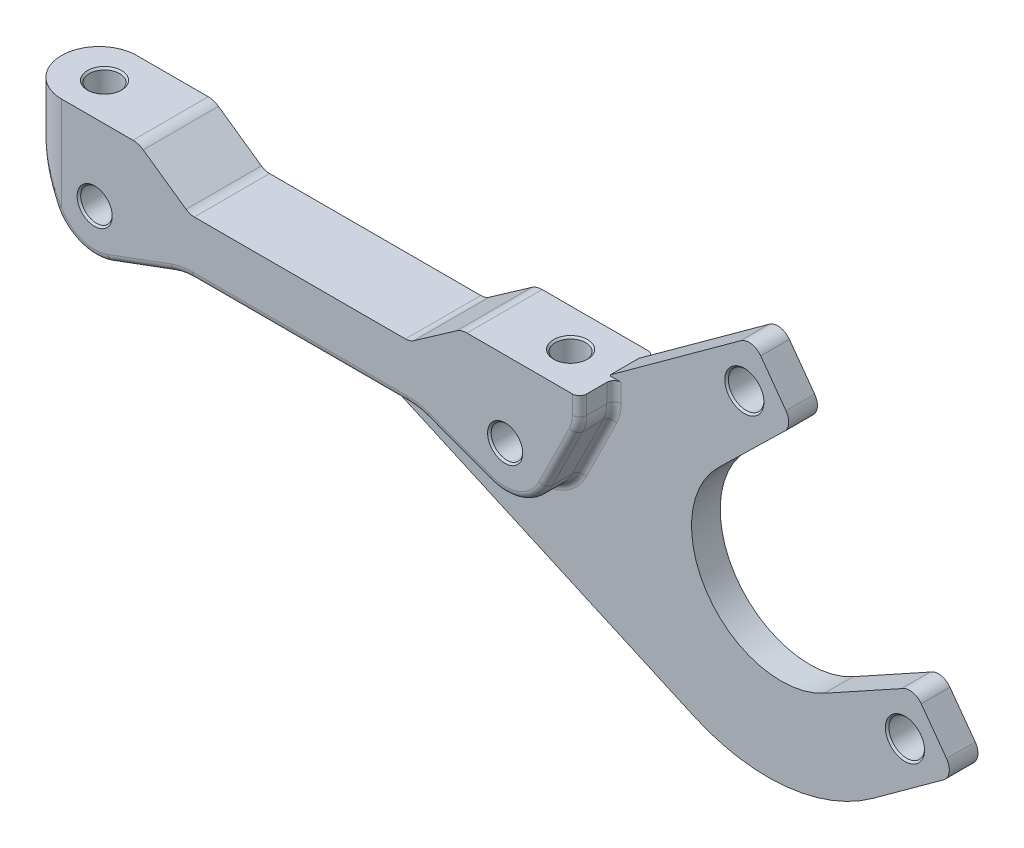
SolidWorks part; units mm, degrees
material "6061-T6 (SS)"
ref_plane "Front Plane" through (0, 0, 0) normal (0, 0, 1) x (1, 0, 0)
ref_plane "Top Plane" through (0, 0, 0) normal (0, 1, 0) x (1, 0, 0)
ref_plane "Right Plane" through (0, 0, 0) normal (1, 0, 0) x (0, 0, -1)
sketch "Sketch1" plane through (0, 0, 0) normal (0, 0, 1) x (1, 0, 0)
  line L0 (-62, 15.9233) -> (-62, -14.304) construction
  line L1 (62, 13.7642) -> (62, -21.0511) construction
  line L2 (-68.4547, -5.5412) -> (-78, 13.76)
  line L3 (-78, 13.76) -> (78, 13.76)
  line L4 (78, 13.76) -> (68.4547, -5.5412)
  line L5 (-73.8283, -12.5) -> (71.5637, -12.5) construction
  line L6 (-26.3177, -4.24) -> (18.9734, -4.24) construction
  line L7 (-30, -4.24) -> (30, -4.24)
  line L8 (-52.9127, -11.7234) -> (-35.2048, -5.1719)
  line L9 (35.2048, -5.1719) -> (52.9127, -11.7234)
  circle A0 centre (-57.25, 0) radius 4.75 construction
  circle A1 centre (57.25, 0) radius 4.75 construction
  arc A2 (-68.4547, -5.5412) -> (-52.9127, -11.7234) centre (-57.25, 0) ccw
  arc A3 (52.9127, -11.7234) -> (68.4547, -5.5412) centre (57.25, 0) ccw
  arc A4 (35.2048, -5.1719) -> (30, -4.24) centre (30, -19.24) ccw
  arc A5 (-30, -4.24) -> (-35.2048, -5.1719) centre (-30, -19.24) ccw
  dimension "D1" = 9.5
  dimension "D2" = 9.5
  dimension "D5" = 25
  dimension "D11" = 15
  dimension "D3" = 124
  dimension "D9" = 156
  dimension "D12" = 60
  dimension "D13" = 30
  dimension "D4" = 62
  dimension "D6" = 18
  dimension "D7" = 26.26
extrude "Boss-Extrude2" add sketch "Sketch1" along normal blind 21
ref_plane "Hub Mounting Plane" through (0, 0, 57) normal (0, 0, 1) x (1, 0, 0)
sketch "Sketch2" plane through (0, 13.76, 0) normal (0, 1, 0) x (1, 0, 0)
  line L0 (78, -21) -> (78, 0) construction
  line L1 (-78, -21) -> (78, -21)
  line L2 (-78, -21) -> (-78, 0)
  line L3 (-78, 0) -> (78, 0)
  line L4 (78, -21) -> (78, 0)
  line L5 (-78, -21) -> (-78, 0) construction
  line L6 (78, -21) -> (-78, -21) construction
  line L7 (78.3439, -10.5) -> (-79.2862, -10.5) construction
  line L8 (78, 0) -> (-78, 0) construction
  circle A0 centre (-65, -10.5) radius 5.05 construction
  circle A1 centre (65, -10.5) radius 5.05 construction
  point P6 (0, 0)
  dimension "D2" = 10.1
  dimension "D3" = 10.1
  dimension "D4" = 130
  dimension "D5" = 65
  dimension "D1" = 10.5
  dimension "D6" = 21
extrude "Boss-Extrude3" add sketch "Sketch2" along normal blind 7.5
fillet "Fillet1" [suppressed] radius 10
sketch "Sketch3" [suppressed] plane through (0, 0, 0) normal (0, 0, -1) x (-1, 0, 0)
  line L0 (-71.9881, 4.5) -> (69.3283, 4.5)
  line L1 (-67.7059, -12.5) -> (67.0774, -12.5) construction
  circle A0 centre (-57.25, 0) radius 4.75
  circle A1 centre (57.25, 0) radius 4.75
  circle A2 centre (-57.25, 0) radius 12.5
  circle A3 centre (57.25, 0) radius 12.5
  arc A4 (-68.4547, -5.5412) -> (-52.9127, -11.7234) centre (-57.25, 0) ccw construction
  dimension "D1" = 17
ref_plane "Plane1" through (0, 0, 0) normal (0, 0, -1) x (-1, 0, 0)
sketch "Sketch5" plane through (0, 21.26, 0) normal (0, 1, 0) x (1, 0, 0)
  circle A0 centre (65, -10.5) radius 5.05 construction
  circle A1 centre (-65, -10.5) radius 5.05 construction
  circle A2 centre (65, -10.5) radius 5.05 construction
  circle A3 centre (-65, -10.5) radius 5.05 construction
sketch "Sketch6" plane through (0, 0, 0) normal (0, 0, -1) x (-1, 0, 0)
  line L2 (29.4573, 11.26) -> (-29.4573, 11.26)
  line L4 (-78, 21.26) -> (78, 21.26) construction
  line L5 (31.7516, 11.9834) -> (45, 21.26)
  line L6 (-45, 21.26) -> (-31.7516, 11.9834)
  line L7 (-45, 21.26) -> (45, 21.26)
  arc A0 (31.7516, 11.9834) -> (29.4573, 11.26) centre (29.4573, 15.26) cw
  arc A1 (-29.4573, 11.26) -> (-31.7516, 11.9834) centre (-29.4573, 15.26) cw
  dimension "D4" = 4
  dimension "D2" = 145
  dimension "D3" = 145
  dimension "D1" = 90
  dimension "D5" = 45
  dimension "D6" = 10
extrude "Cut-Extrude3" cut sketch "Sketch6" against normal up to surface (21 mm away) up to face at (0, 0.932, 21)
fillet "Fillet3" radius 5 2 edges at (-45, 21.26, 10.5) (45, 21.26, 10.5)
fillet "Fillet4" radius 10 2 edges at (-78, 13.76, 10.5) (78, 13.76, 10.5)
sketch "Sketch8" plane through (0, 21.26, 0) normal (0, 1, 0) x (1, 0, 0)
  line L1 (-78, 0) -> (-78, -21)
  line L6 (-65, -10.5) -> (-66.5, -10.5) construction
  line L9 (-77, -0.6837) -> (-77, -19.879) construction
  line L10 (-66.5, 0) -> (-78, 0)
  line L11 (-78, -21) -> (-66.5, -21)
  line L12 (0, 15.9579) -> (0, -40.4638) construction
  arc A5 (-66.5, 0) -> (-66.5, -21) centre (-66.5, -10.5) ccw
  point P6 (-65.75, -10.5)
  dimension "D1" = 12
extrude "Cut-Extrude4" cut sketch "Sketch8" against normal blind 34
hole_wizard "M10x1.5 Tapped Hole2" positions "3DSketch3" profile "Sketch12" tap size "M10x1.5" standard "ANSI Metric"
sketch3d "3DSketch3"
  point P0 (65, 21.26, 10.5)
  point P3 (-65, 21.26, 10.5)
  point P5 (-65, 21.26, 10.5)
  point P7 (-65, 21.26, 10.5)
cosmetic thread "Hole Thread5" parameters "D1"=20, "D2"=10
cosmetic thread "Hole Thread6" parameters "D1"=20, "D2"=10
cosmetic thread "Hole Thread7" parameters "D1"=20, "D2"=10
cosmetic thread "Hole Thread8" parameters "D1"=20, "D2"=10
sketch "Sketch12" plane through (65, 21.26, 10.5) normal (1, 0, 0) x (0, 0, 1)
  line L0 (0, 0) -> (0, 16.0537)
  line L1 (0, 16.0537) -> (4.25, 13.5)
  line L2 (4.25, 13.5) -> (4.25, 0)
  line L5 (4.25, 0) -> (0, 0)
  line L10 (0, 16.0537) -> (-4.25, 13.5) construction
  line L11 (0, -6.35) -> (0, 107.95) construction
  dimension "Tap Drill Dia." = 8.5
  dimension "Tap Drill Depth" = 13.5
  dimension "Drill Angle" = 118
chamfer "Chamfer2" distance 0.5 angle 45 2 edges at (-65, 21.26, 14.75) (65, 21.26, 14.75)
hole_wizard "M10x1.25 Tapped Hole1" positions "Sketch17" profile "Sketch18" tap size "M10x1.25" standard "ANSI Metric" end condition through all
sketch "Sketch17" plane through (0, 0, 0) normal (0, 0, -1) x (-1, 0, 0)
  point P0 (-57.25, 0)
  point P3 (57.25, 0)
sketch "Sketch18" plane through (57.25, 0, 0) normal (1, 0, 0) x (0, 1, 0)
  line L0 (0, 0) -> (0, 21)
  line L1 (0, 21) -> (4.4, 21)
  line L2 (4.4, 21) -> (4.4, 0)
  line L5 (4.4, 0) -> (0, 0)
  line L11 (0, -6.35) -> (0, 107.95) construction
  dimension "Thru Tap Drill Dia." = 8.8
  dimension "Thru Tap Drill Depth" = 21
cosmetic thread "Hole Thread3" parameters "D2"=10
cosmetic thread "Hole Thread10" parameters "D2"=10
ref_plane "Plane3" through (0, 0, 11.4) normal (0, 0, 1) x (1, 0, 0)
chamfer "Chamfer3" distance 0.5 angle 45 2 edges at (-61.65, 0, 21) (52.85, 0, 21)
sketch "Sketch19" plane through (0, 0, 11.4) normal (0, 0, 1) x (1, 0, 0)
  line L3 (100.4018, -49.281) -> (0, -4.24)
  line L8 (125.9954, 37.394) -> (118.942, 47.1022)
  line L10 (77, 33.4551) -> (77, 21.26) construction
  line L14 (58.8815, -52.0577) -> (191.3568, 45.5598) construction
  line L15 (69.75, 21.26) -> (60.25, 21.26) construction
  line L19 (113.3548, 47.9871) -> (77, 21.5738)
  line L22 (158.144, -13.66) -> (136.7247, -25.4871)
  line L23 (170.7846, -24.2531) -> (163.7312, -14.5449)
  line L24 (171.821, -32.4848) -> (154.5369, -8.6953) construction
  line L25 (169.8997, -29.8403) -> (150.2564, -44.112)
  line L26 (125.1105, 31.8068) -> (107.1704, 14.2812)
  line L27 (128.9273, -14.7549) -> (169.2983, -70.3208) construction
  line L28 (77, 21.5738) -> (77, 21.26)
  line L29 (77, 21.26) -> (78, 21.26)
  line L30 (78, 21.26) -> (78, 16.0976)
  line L31 (78, 21.26) -> (78, 16.0976) construction
  line L32 (68.4547, -5.5412) -> (76.9637, 11.6646)
  line L33 (68.4547, -5.5412) -> (76.9637, 11.6646) construction
  line L34 (52.9127, -11.7234) -> (35.2048, -5.1719)
  line L35 (35.2048, -5.1719) -> (52.9127, -11.7234) construction
  line L36 (-30, -4.24) -> (30, -4.24) construction
  line L37 (0, -4.24) -> (30, -4.24)
  line L38 (0, 4.4203) -> (0, -17.9644) construction
  arc A0 (170.2177, -3.8157) -> (138.204, 40.2475) centre (65.9033, -45.9433) ccw construction
  arc A5 (107.1704, 14.2812) -> (136.7247, -25.4871) centre (124.6402, -3.6018) ccw
  circle A10 centre (159.1678, -25.2769) radius 5 construction
  arc A12 (163.7312, -14.5449) -> (158.144, -13.66) centre (160.4952, -16.896) ccw
  circle A13 centre (114.3785, 36.3702) radius 5 construction
  arc A18 (113.3548, 47.9871) -> (118.942, 47.1022) centre (115.7059, 44.7511) cw
  arc A20 (170.7846, -24.2531) -> (169.8997, -29.8403) centre (167.5486, -26.6042) cw
  arc A21 (100.4018, -49.281) -> (150.2564, -44.112) centre (120.8672, -3.6611) ccw
  arc A22 (125.9954, 37.394) -> (125.1105, 31.8068) centre (122.7593, 35.0428) cw
  arc A23 (76.9637, 11.6646) -> (78, 16.0976) centre (68, 16.0976) ccw
  arc A24 (76.9637, 11.6646) -> (78, 16.0976) centre (68, 16.0976) ccw construction
  arc A25 (52.9127, -11.7234) -> (68.4547, -5.5412) centre (57.25, 0) ccw
  arc A26 (52.9127, -11.7234) -> (68.4547, -5.5412) centre (57.25, 0) ccw construction
  arc A27 (35.2048, -5.1719) -> (30, -4.24) centre (30, -19.24) ccw
  arc A28 (35.2048, -5.1719) -> (30, -4.24) centre (30, -19.24) ccw construction
  point P20 (156.9177, 20.1825)
  dimension "D2" = 4
  dimension "D4" = 50
  dimension "D3" = 4
  dimension "D8" = 4
  dimension "D9" = 4
  dimension "D6" = 25
  dimension "D10" = 10
  dimension "D7" = 10
  dimension "D12" = 10
  dimension "D5" = 10
  dimension "D11" = 20
  dimension "D13" = 20
  dimension "D14" = 12
extrude "Willwood_LobsterClaw" add sketch "Sketch19" against normal blind 8
sketch "Sketch26" plane through (0, 0, 3.4) normal (0, 0, -1) x (-1, 0, 0)
  line L0 (-70, -24.6823) -> (-133.8678, -53.3339) construction
  line L1 (0, -4.24) -> (-100.4018, -49.281) construction
  line L2 (0, -4.24) -> (-100.4018, -49.281) construction
  line L3 (0, -4.24) -> (-100.4018, -49.281) construction
  text T1 "R" font "Tahoma" height in points 48
  dimension "D1" = 10
  dimension "D2" = 70
  dimension "D3" = 40
extrude "Cut-Extrude7" cut sketch "Sketch26" against normal blind 0.3
hole_wizard "7/16-20 Tapped Hole1" positions "Sketch35" profile "Sketch36" tap size "7/16-20" standard "ANSI Inch" end condition through all
sketch "Sketch35" plane through (0, 0, 3.4) normal (0, 0, -1) x (-1, 0, 0)
  point P0 (-114.3785, 36.3702)
  point P2 (-159.1678, -25.2769)
sketch "Sketch36" plane through (114.3785, 36.3702, 3.4) normal (1, 0, 0) x (0, 1, 0)
  line L0 (0, 0) -> (0, 17.6)
  line L1 (0, 17.6) -> (4.9606, 17.6)
  line L2 (4.9606, 17.6) -> (4.9606, 0)
  line L5 (4.9606, 0) -> (0, 0)
  line L11 (0, -6.35) -> (0, 107.95) construction
  dimension "Thru Tap Drill Dia." = 9.9212
  dimension "Thru Tap Drill Depth" = 17.6
cosmetic thread "Hole Thread11" parameters "D1"=22.23, "D2"=10.9212
cosmetic thread "Hole Thread12" parameters "D1"=22.23, "D2"=10.9212
chamfer "Chamfer4" distance 0.5 angle 45 2 edges at (154.2071, -25.2769, 11.4) (109.4179, 36.3702, 11.4)
fillet "Fillet29" radius 2 25 edges at (78, 18.6788, 0) (77.7375, 13.8214, 0) (72.7092, 3.0617, 0) (61.8701, -11.6149, 0) (44.0587, -8.4477, 0) (32.6438, -4.4748, 0) (0, -4.24, 0) (-32.6438, -4.4748, 0) (-44.0587, -8.4477, 0) (-60.2135, -12.1436, 0) (-74.3009, 6.2803, 3.4718) (-74.3009, 6.2803, 17.5282) (-60.2135, -12.1436, 21) (-44.0587, -8.4477, 21) (-32.6438, -4.4748, 21) (78, 18.6788, 21) (77.7375, 13.8214, 21) (72.7092, 3.0617, 21) (61.8701, -11.6149, 21) (44.0587, -8.4477, 21) (32.6438, -4.4748, 21) (0, -4.24, 21)
fillet "Fillet30" radius 2 7 edges at (78, 18.6788, 11.4) (77.7375, 13.8214, 11.4) (32.6438, -4.4748, 11.4) (44.0587, -8.4477, 11.4) (61.8701, -11.6149, 11.4) (72.7092, 3.0617, 11.4) (15, -4.24, 11.4)
fillet "Fillet31" radius 2 7 edges at (78, 18.6788, 3.4) (77.7375, 13.8214, 3.4) (32.6438, -4.4748, 3.4) (44.0587, -8.4477, 3.4) (61.8701, -11.6149, 3.4) (72.7092, 3.0617, 3.4) (15, -4.24, 3.4)
equation "\"D4@Sketch1\"=\"D3@Sketch1\"/2"
equation "\"D5@Sketch2\"=\"D4@Sketch2\"/2"
equation "\"D13@Sketch1\"=\"D12@Sketch1\"/2"
equation "\"D5@Sketch6\"=\"D1@Sketch6\"/2"
equation "\"D1@Sketch2\"=\"D6@Sketch2\"/2"
equation "\"D8@Sketch19\"=\"D3@Sketch19\""
equation "\"D9@Sketch19\"=\"D2@Sketch19\""
equation "\"D12@Sketch19\"=\"D10@Sketch19\""
equation "\"D13@Sketch19\"=\"D11@Sketch19\""
equation "\"D4@Sketch19\"=\"D6@Sketch19\"*2"
